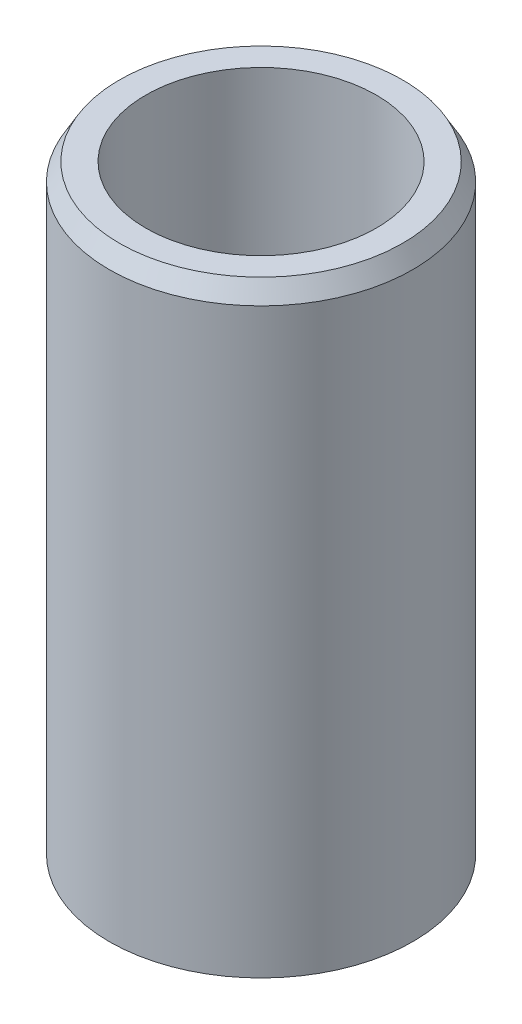
SolidWorks part; units mm, degrees
ref_plane "Front Plane" through (0, 0, 0) normal (0, 0, 1) x (1, 0, 0)
ref_plane "Top Plane" through (0, 0, 0) normal (0, 1, 0) x (1, 0, 0)
ref_plane "Right Plane" through (0, 0, 0) normal (1, 0, 0) x (0, 0, -1)
sketch "Sketch1" plane through (0, 0, 0) normal (0, 1, 0) x (1, 0, 0)
  circle A0 centre (0, 0) radius 45
  dimension "SHAFT_OD" = 90
extrude "Boss-Extrude1" add sketch "Sketch1" along normal blind 180.8288
sketch "Sketch2" plane through (0, 0, 0) normal (0, 1, 0) x (1, 0, 0)
  circle A0 centre (0, 0) radius 34.1831
  dimension "BORE_D" = 68.3662
extrude "Cut-Extrude1" cut sketch "Sketch2" along normal through all
chamfer "Chamfer1" distance 5.2423 angle 30 2 edges at (0, 180.8288, 45) (0, 0, 45) first distance on face at (0, 180.8288, 45) first distance on face at (0, 0, 34.1831)
